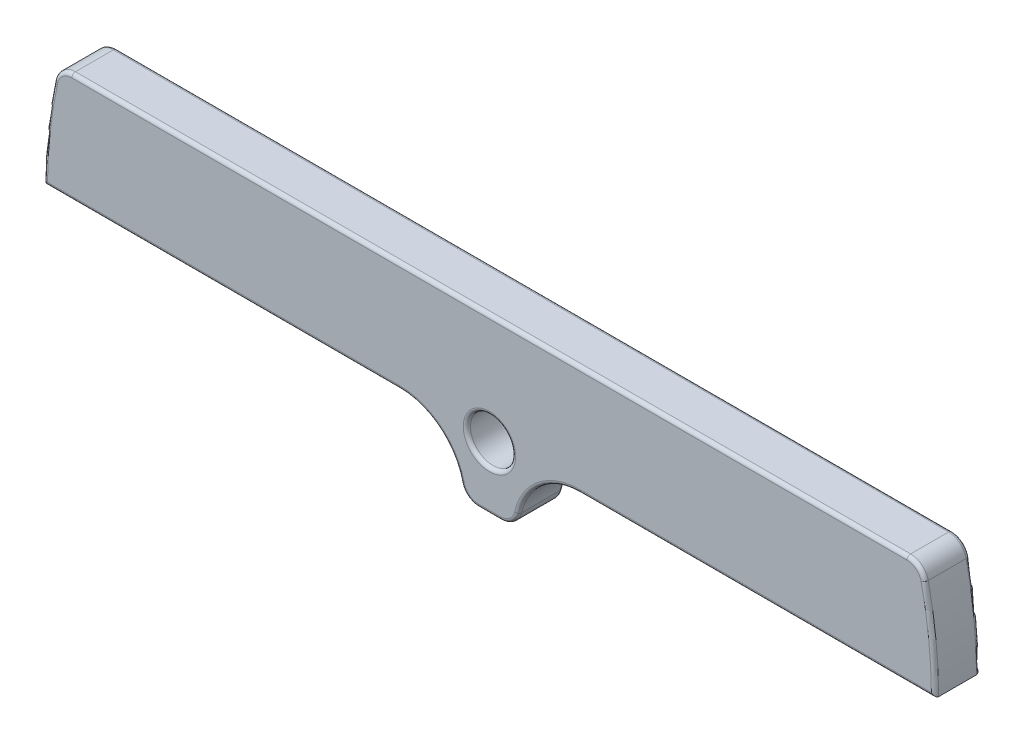
SolidWorks part; units mm, degrees
ref_plane "Front Plane" through (0, 0, 0) normal (0, 0, 1) x (1, 0, 0)
ref_plane "Top Plane" through (0, 0, 0) normal (0, 1, 0) x (1, 0, 0)
ref_plane "Right Plane" through (0, 0, 0) normal (1, 0, 0) x (0, 0, -1)
sketch "Sketch1" plane through (0, 0, 0) normal (0, 0, 1) x (1, 0, 0)
  line L0 (0, 12.7) -> (50.0063, 12.7)
  line L1 (0, 0) -> (125.4125, 0) construction
  line L3 (1.9294, 28.1354) -> (123.4831, 28.1354)
  line L5 (62.7063, 28.1354) -> (62.7062, 0) construction
  line L6 (50.0063, 28.1354) -> (50.0063, 0) construction
  line L7 (75.4063, 28.1354) -> (75.4063, 0) construction
  line L8 (58.8962, 3.81) -> (66.5163, 3.81)
  line L9 (0, 12.7) -> (125.4125, 12.7) construction
  line L10 (75.4063, 12.7) -> (125.4125, 12.7)
  circle A0 centre (62.7063, 12.7) radius 3.175
  arc A1 (75.4063, 12.7) -> (66.5163, 3.81) centre (75.4063, 3.81) ccw
  arc A2 (58.8962, 3.81) -> (50.0063, 12.7) centre (50.0063, 3.81) ccw
  arc A3 (1.9294, 28.1354) -> (0, 12.7) centre (62.7063, 12.7) ccw
  arc A4 (125.4125, 12.7) -> (123.4831, 28.1354) centre (62.7063, 12.7) ccw
  dimension "D4" = 6.35
  dimension "D7" = 17.78
  dimension "D8" = 17.78
  dimension "D1" = 125.4125
  dimension "D3" = 12.7
  dimension "D5" = 12.7
  dimension "D6" = 12.7
extrude "Extrude1" add sketch "Sketch1" along normal blind 6.35
fillet "Fillet1" radius 2.54 4 edges at (123.4831, 28.1354, 3.175) (1.9294, 28.1354, 3.175) (66.5163, 3.81, 3.175) (58.8962, 3.81, 3.175)
fillet "Fillet2" radius 0.508 26 edges at (65.8813, 12.7, 0) (100.4094, 12.7, 0) (125.0471, 19.4593, 0) (123.0663, 27.5746, 0) (62.7063, 28.1354, 0) (2.3462, 27.5746, 0) (0.3654, 19.4593, 0) (25.0031, 12.7, 0) (55.5501, 10.7596, 0) (59.5665, 4.3644, 0) (62.7063, 3.81, 0) (65.846, 4.3644, 0) (69.8624, 10.7596, 0) (65.8813, 12.7, 6.35) (59.5665, 4.3644, 6.35) (55.5501, 10.7596, 6.35) (25.0031, 12.7, 6.35) (0.3654, 19.4593, 6.35) (2.3462, 27.5746, 6.35) (62.7063, 28.1354, 6.35) (123.0663, 27.5746, 6.35) (125.0471, 19.4593, 6.35) (100.4094, 12.7, 6.35) (69.8624, 10.7596, 6.35) (65.846, 4.3644, 6.35) (62.7063, 3.81, 6.35)
